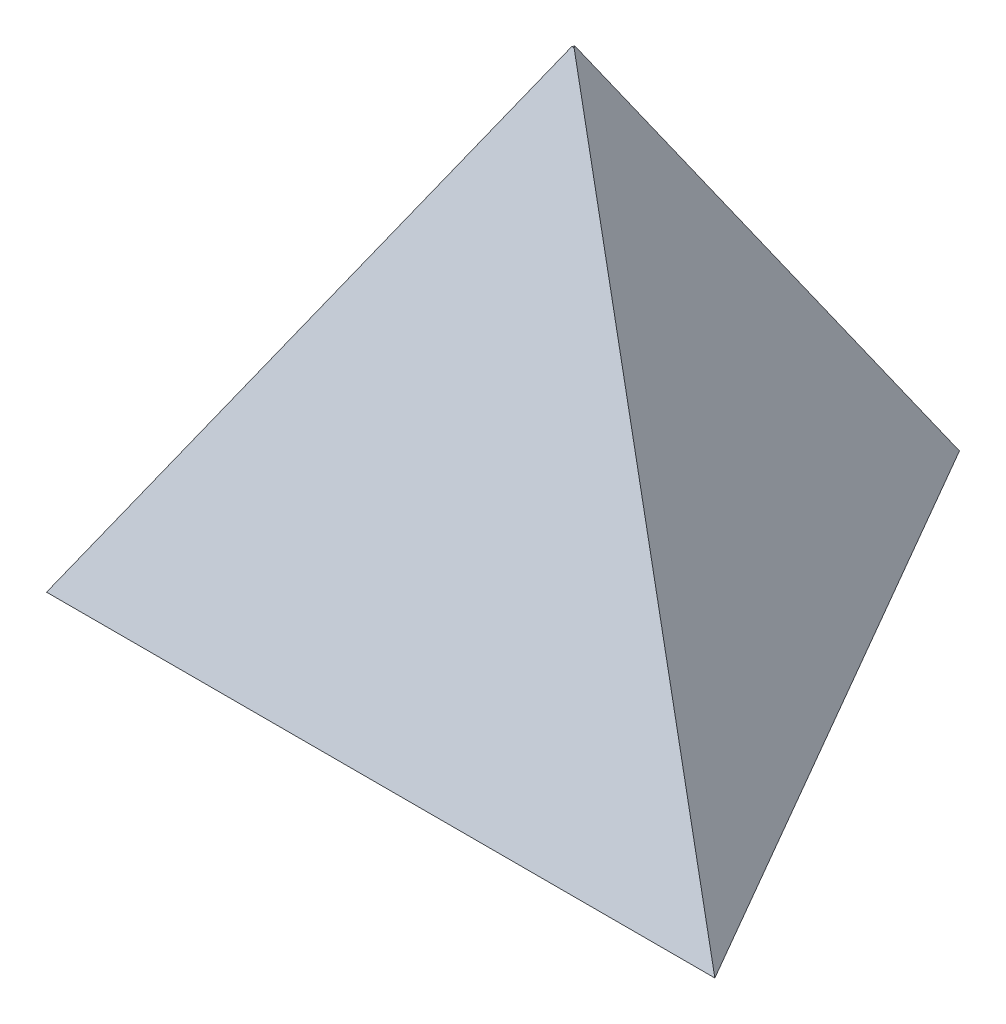
SolidWorks part; units mm, degrees
ref_plane "Front Plane" through (0, 0, 0) normal (0, 0, 1) x (1, 0, 0)
ref_plane "Top Plane" through (0, 0, 0) normal (0, 1, 0) x (1, 0, 0)
ref_plane "Right Plane" through (0, 0, 0) normal (1, 0, 0) x (0, 0, -1)
sketch "Sketch1" plane through (0, 0, 0) normal (0, 1, 0) x (1, 0, 0)
  line L1 (40, -23.094) -> (0, 46.188)
  line L2 (0, 46.188) -> (-40, -23.094)
  line L3 (-40, -23.094) -> (40, -23.094)
  circle A0 centre (0, 0) radius 23.094 construction
  dimension "D1" = 80
extrude "Boss-Extrude1" add sketch "Sketch1" along normal blind 65 draft 19.5
shell "Shell1" thickness 2 removed face at (0, 0, 0)
ref_plane "Plane2" through (0, 0, -46.188) normal (-0.5, 0, 0.866) x (0.866, 0, 0.5)
sketch "Sketch4" plane through (0, 0, 0) normal (0, 1, 0) x (1, 0, 0)
  line L4 (30, -17.3205) -> (0, 34.641)
  line L5 (0, 34.641) -> (-30, -17.3205)
  line L6 (37.1911, -21.4723) -> (0, 42.9446)
  line L7 (-37.1911, -21.4723) -> (37.1911, -21.4723)
  line L8 (0, 42.9446) -> (-37.1911, -21.4723)
  line L9 (37.1911, -21.4723) -> (0, 42.9446)
  line L10 (-37.1911, -21.4723) -> (37.1911, -21.4723)
  line L11 (0, 42.9446) -> (-37.1911, -21.4723)
  line L12 (-30, -17.3205) -> (30, -17.3205)
  circle A0 centre (0, 0) radius 17.3205 construction
  dimension "D2" = 60
  dimension "D1" = 0.5
extrude "Cut-Extrude1" cut sketch "Sketch4" along normal blind 5 draft 19.5
sketch "Sketch6" plane through (0, 0, 0) normal (0, -1, 0) x (1, 0, 0)
  line L1 (30, 17.3205) -> (-30, 17.3205)
  line L2 (-30, 17.3205) -> (0, -34.641)
  line L3 (0, -34.641) -> (30, 17.3205)
  circle A0 centre (0, 0) radius 17.3205 construction
  dimension "D1" = 60
extrude "Cut-Extrude2" cut sketch "Sketch6" against normal blind 11
